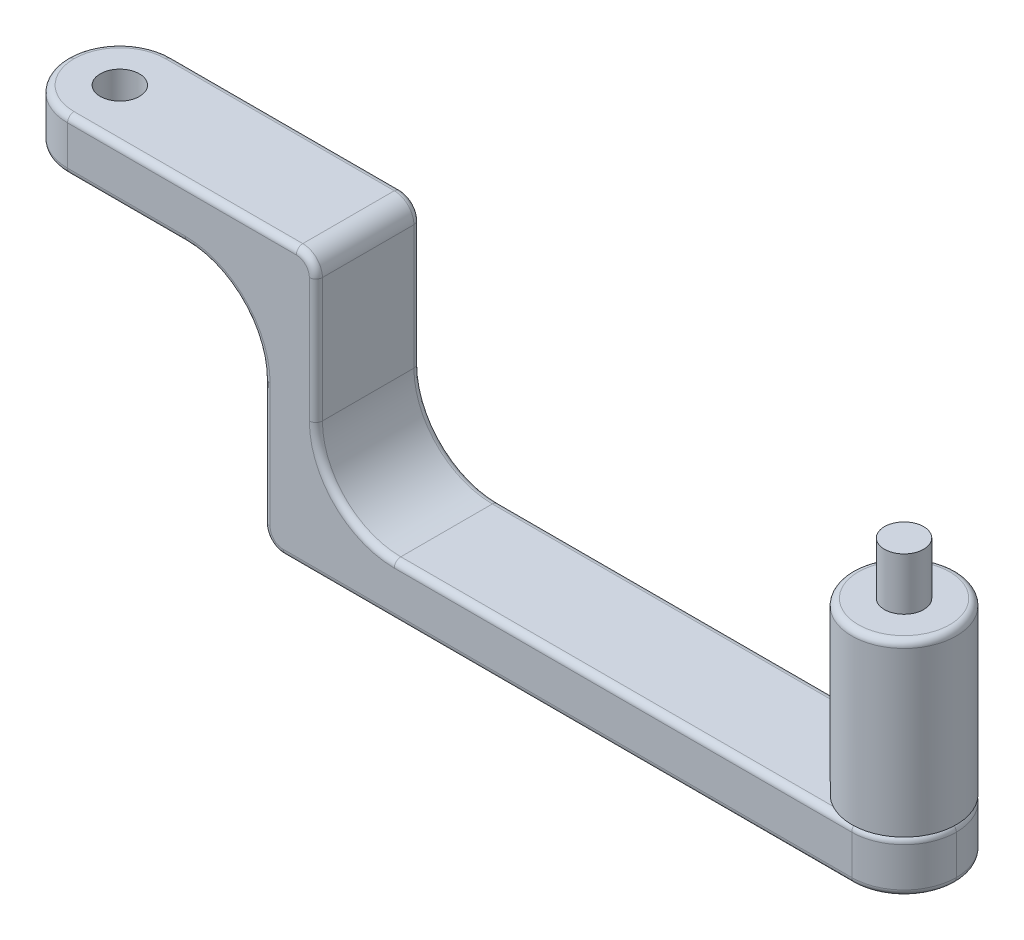
SolidWorks part; units mm, degrees
ref_plane "Front Plane" through (0, 0, 0) normal (0, 0, 1) x (1, 0, 0)
ref_plane "Top Plane" through (0, 0, 0) normal (0, 1, 0) x (1, 0, 0)
ref_plane "Right Plane" through (0, 0, 0) normal (1, 0, 0) x (0, 0, -1)
sketch "Sketch1" plane through (0, 0, 0) normal (0, 0, 1) x (1, 0, 0)
  line L0 (0, 20) -> (0, -20) construction
  line L1 (0, 0) -> (600, 0) construction
  line L2 (0, -20) -> (-40, -20)
  line L3 (-40, -20) -> (-40, 20)
  line L4 (-40, 20) -> (0, 20)
  line L5 (0, 20) -> (175, 20)
  line L6 (190, 5) -> (190, -90)
  line L7 (250, -150) -> (640, -150)
  line L8 (640, -150) -> (640, -190)
  line L9 (640, -190) -> (165, -190)
  line L10 (150, -175) -> (150, -80)
  line L11 (90, -20) -> (0, -20)
  line L12 (150, -20) -> (190, -20) construction
  line L13 (600, 0) -> (600, -150) construction
  arc A0 (250, -150) -> (190, -90) centre (250, -90) cw
  arc A1 (150, -80) -> (90, -20) centre (90, -80) ccw
  arc A2 (165, -190) -> (150, -175) centre (165, -175) cw
  arc A3 (190, 5) -> (175, 20) centre (175, 5) ccw
  point P4 (0, 0)
  dimension "D2" = 60
  dimension "D5" = 15
  dimension "D1" = 40
  dimension "D3" = 150
  dimension "D4" = 40
  dimension "D6" = 150
  dimension "D7" = 600
extrude "Boss-Extrude1" add sketch "Sketch1" along normal mid plane 80
sketch "Sketch2" plane through (0, -150, 0) normal (0, 1, 0) x (1, 0, 0)
  line L0 (0, 0) -> (600, 0) construction
  line L1 (640, -40) -> (640, 40) construction
  circle A0 centre (600, 0) radius 40
  dimension "D1" = 600
extrude "Boss-Extrude2" add sketch "Sketch2" along normal up to surface (170 mm away) separate body up to face at (67.5, 20, 0)
sketch "Sketch3" plane through (0, 20, 0) normal (0, 1, 0) x (1, 0, 0)
  circle A0 centre (600, 0) radius 15
  circle A1 centre (600, 0) radius 40
  circle A2 centre (600, 0) radius 40 construction
  dimension "D1" = 30
extrude "Cut-Extrude1" cut sketch "Sketch3" against normal up to surface (40 mm away) up to face at (25, -20, 0)
sketch "Sketch4" plane through (0, 20, 0) normal (0, 1, 0) x (1, 0, 0)
  circle A0 centre (0, 0) radius 15
  circle A1 centre (600, 0) radius 15 construction
extrude "Cut-Extrude2" cut sketch "Sketch4" against normal through all
fillet "Fillet1" radius 40 2 edges at (640, -170, 40) (640, -170, -40)
fillet "Fillet2" radius 40 2 edges at (-40, 0, 40) (-40, 0, -40)
fillet "Fillet3" radius 5 1 edges at (560, -20, 0)
fillet "Fillet4" radius 5 28 edges at (154.3934, -185.6066, -40) (150, -127.5, -40) (132.4264, -37.5736, -40) (45, -20, -40) (-28.2843, -20, -28.2843) (-28.2843, -20, 28.2843) (45, -20, 40) (132.4264, -37.5736, 40) (150, -127.5, 40) (154.3934, -185.6066, 40) (382.5, -190, 40) (628.2843, -190, 28.2843) (628.2843, -190, -28.2843) (185.6066, 15.6066, -40) (190, -42.5, -40) (207.5736, -132.4264, -40) (425, -150, -40) (628.2843, -150, -28.2843) (628.2843, -150, 28.2843) (425, -150, 40) (207.5736, -132.4264, 40) (190, -42.5, 40) (185.6066, 15.6066, 40) (87.5, 20, 40) (-28.2843, 20, 28.2843) (-28.2843, 20, -28.2843) (382.5, -190, -40) (87.5, 20, -40)
